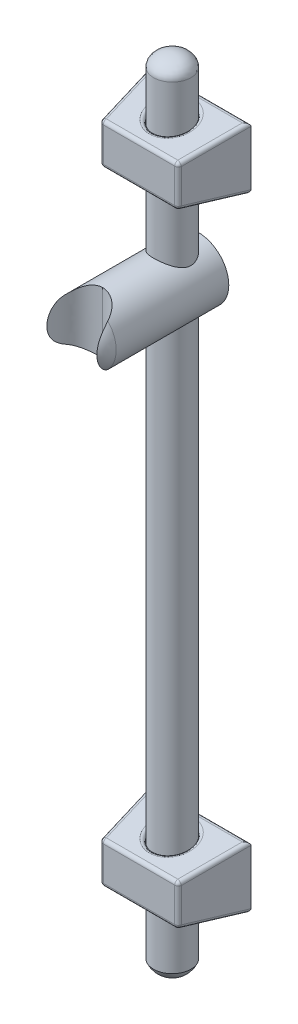
SolidWorks part; units mm, degrees
ref_plane "Front Plane" through (0, 0, 0) normal (0, 0, 1) x (1, 0, 0)
ref_plane "Top Plane" through (0, 0, 0) normal (0, 1, 0) x (1, 0, 0)
ref_plane "Right Plane" through (0, 0, 0) normal (1, 0, 0) x (0, 0, -1)
ref_plane "Plane1" through (0, -70, 0) normal (0, 1, 0) x (-1, 0, 0)
sketch "Sketch1" plane through (0, 0, 0) normal (0, 0, 1) x (1, 0, 0)
  line L0 (-206.0311, 0) -> (256.8661, 0) construction
  line L1 (-40, -500) -> (40, -500)
  line L2 (-40, -500) -> (-40, -450)
  line L4 (40, -500) -> (40, -450)
  line L5 (40, -500) -> (40, -450)
  line L6 (-40, -450) -> (40, -450)
  line L13 (-40, -500) -> (40, -500)
  line L17 (-40, 0) -> (40, 0)
  line L18 (-40, 0) -> (-40, 50)
  line L19 (-40, 50) -> (40, 50)
  line L20 (40, 0) -> (40, 50)
  point P0 (0, 0)
  dimension "D1" = 50
extrude "Boss-Extrude1" add sketch "Sketch1" along normal blind 50 draft 10 contours L6 L2 L1 L4 | L19 L20 L17 L18 region at (0, -475, 0)
sketch "Sketch2" plane through (0, 0, 0) normal (0, 1, 0) x (1, 0, 0)
  circle A0 centre (0, -23.297) radius 15
  dimension "D1" = 30
extrude "Cut-Extrude1" cut sketch "Sketch2" against normal mid plane 1160
extrude "Boss-Extrude3" add sketch "Sketch2<2>" against normal blind 540 separate body
sketch "Sketch2<2>" plane through (0, 0, 0) normal (0, 1, 0) x (1, 0, 0) same geometry as "Sketch2"
sketch "Sketch3" plane through (0, -70, 0) normal (0, 1, 0) x (1, 0, 0)
  line L1 (0, -110.8221) -> (0, -8.297)
  line L3 (24.468, -8.297) -> (24.468, -92.7809)
  line L4 (0, -8.297) -> (0, -2.3883)
  line L5 (0, -2.3883) -> (24.468, -2.3883)
  line L6 (24.468, -2.3883) -> (24.468, -8.297)
  circle A1 centre (0, -23.297) radius 15 construction
  arc A2 (24.468, -92.7809) -> (0, -110.8221) centre (4.52, -91.3395) cw
  dimension "D1" = 20
sketch "Sketch7" plane through (0, 0, 0) normal (0, 1, 0) x (1, 0, 0)
  circle A0 centre (0, -23.297) radius 15
extrude "Boss-Extrude4" add sketch "Sketch7" along normal blind 80 separate body
sketch "Sketch8" plane through (0, -70, 0) normal (0, 1, 0) x (-1, 0, 0)
  line L0 (0, 195.96) -> (0, -119.5314) construction
revolve "Revolve1" add sketch "Sketch3" angle 360 about L0
sketch "Sketch6" plane through (0, -70, 0) normal (0, 1, 0) x (1, 0, 0)
  line L0 (0, -70.563) -> (0, -135.8312) construction
  line L2 (0, -122.9218) -> (-20, -122.9218)
  line L3 (0, -122.9218) -> (20, -122.9218)
  spline S0 degree 2 poles (-20, -122.9218) (-23.5533, -79.9272) (0, -79.133) knots 0 0 0 0.96785 0.96785 0.96785
  spline S1 degree 2 poles (20, -122.9218) (23.5533, -79.9272) (0, -79.133) knots 0 0 0 0.96785 0.96785 0.96785
  dimension "D1" = 20
extrude "Cut-Extrude3" cut sketch "Sketch6" against normal mid plane 50
dome "Dome1" faces to dome 1 distance 10 reverse direction no elliptical dome no face at (0, -540, 38.297) parameters "D1"=10
dome "Dome2" faces to dome 1 distance 10 reverse direction no elliptical dome yes face at (0, 80, 38.297) parameters "D1"=10
fillet "Fillet1" radius 3 12 edges at (-35.5918, 4.4082, 25) (35.5918, 4.4082, 25) (0, 0, 0) (0, 6.7528, 38.297) (35.5918, 45.5918, 25) (-35.5918, 45.5918, 25) (0, 50, 0) (0, 48.537, 8.297) (0, 41.1837, 50) (31.1837, 25, 50) (0, 8.8163, 50) (-31.1837, 25, 50)
fillet "Fillet2" radius 3 12 edges at (-35.5918, -495.5918, 25) (35.5918, -495.5918, 25) (0, -500, 0) (0, -493.2472, 38.297) (31.1837, -475, 50) (0, -491.1837, 50) (-31.1837, -475, 50) (35.5918, -454.4082, 25) (0, -458.8163, 50) (-35.5918, -454.4082, 25) (0, -450, 0) (0, -451.463, 8.297)
